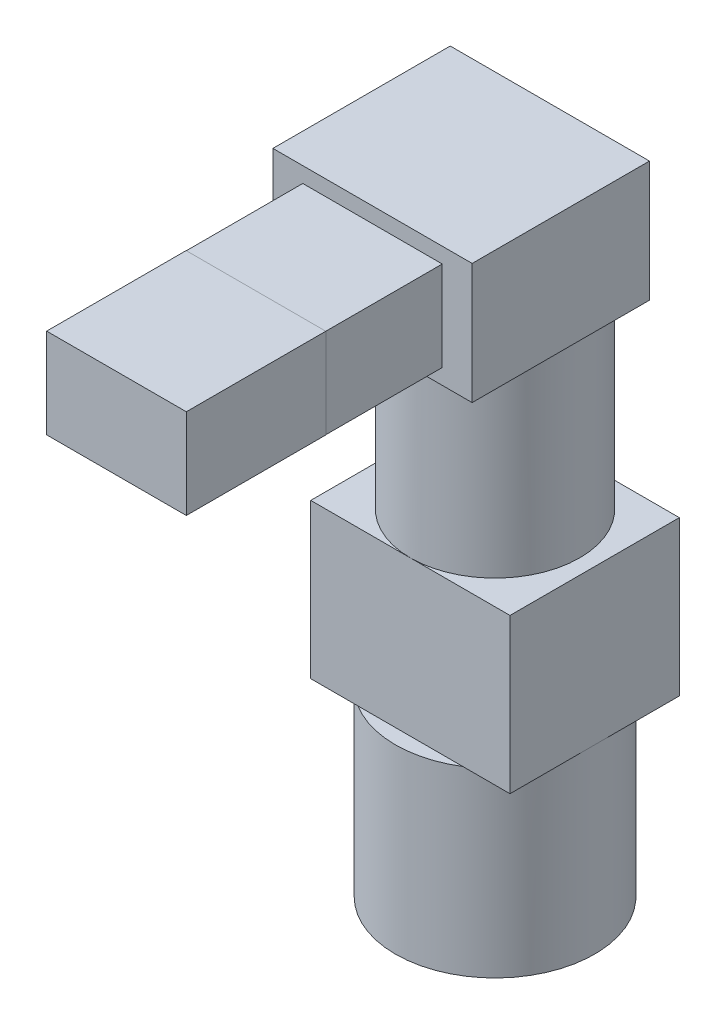
SolidWorks part; units mm, degrees
ref_plane "Front Plane" through (0, 0, 0) normal (0, 0, 1) x (1, 0, 0)
ref_plane "Top Plane" through (0, 0, 0) normal (0, 1, 0) x (1, 0, 0)
ref_plane "Right Plane" through (0, 0, 0) normal (1, 0, 0) x (0, 0, -1)
sketch "Sketch1" plane through (0, 0, 0) normal (0, 1, 0) x (1, 0, 0)
  circle A0 centre (0, 0) radius 50
extrude "Boss-Extrude1" add sketch "Sketch1" along normal blind 91
sketch "Sketch2" plane through (0, 0, 0) normal (1, 0, 0) x (0, 0, -1)
  line L0 (0, 47.4071) -> (0, 172.9241) construction
  line L1 (0, 50.05) -> (0, -50.05) construction
  line L2 (50, 91) -> (-50, 91) construction
  line L3 (42.5, 91) -> (-42.5, 91)
  line L4 (42.5, 91) -> (42.5, 168.5)
  line L5 (42.5, 168.5) -> (-42.5, 168.5)
  line L6 (-42.5, 91) -> (-42.5, 168.5)
  point P12 (0, 168.5)
  dimension "D1" = 77.5
  dimension "D2" = 85
extrude "Boss-Extrude2" add sketch "Sketch2" along normal blind 50 and the other way blind 50
ref_plane "Plane1" through (0, 135.5, 0) normal (0, 1, 0) x (1, 0, 0)
sketch "Sketch4" plane through (0, 135.5, 0) normal (0, 1, 0) x (1, 0, 0)
  circle A0 centre (0, 0) radius 42.5
extrude "Boss-Extrude3" add sketch "Sketch4" along normal blind 135
sketch "Sketch5" plane through (0, 0, 0) normal (1, 0, 0) x (0, 0, -1)
  line L0 (0, 248.4844) -> (0, 367.9713) construction
  line L1 (0, 55) -> (0, -55) construction
  line L2 (42.5, 270.5) -> (-42.5, 270.5) construction
  line L7 (-61.5, 331) -> (27.5, 331)
  line L8 (-61.5, 331) -> (-61.5, 270.5)
  line L9 (-61.5, 270.5) -> (27.5, 270.5)
  line L10 (27.5, 331) -> (27.5, 270.5)
  dimension "D1" = 61.5
  dimension "D2" = 89
  dimension "D3" = 60.5
extrude "Boss-Extrude4" add sketch "Sketch5" along normal blind 50 and the other way blind 50
ref_plane "Plane2" through (0, 300.75, 0) normal (0, 1, 0) x (1, 0, 0)
sketch "Sketch6" plane through (0, 0, 61.5) normal (0, 0, 1) x (1, 0, 0)
  line L0 (48.95, 300.75) -> (-48.95, 300.75) construction
  line L1 (-35, 323.25) -> (35, 323.25)
  line L2 (-35, 323.25) -> (-35, 278.25)
  line L3 (-35, 278.25) -> (35, 278.25)
  line L4 (35, 323.25) -> (35, 278.25)
  line L5 (-35, 323.25) -> (35, 278.25) construction
  line L6 (-35, 278.25) -> (35, 323.25) construction
  line L7 (0, -61.325) -> (0, 61.325) construction
  point P0 (0, 300.75)
  dimension "D1" = 45
  dimension "D2" = 70
extrude "Boss-Extrude5" add sketch "Sketch6" along normal blind 58.5
sketch "Sketch7" plane through (0, 0, 120) normal (0, 0, 1) x (1, 0, 0)
  line L0 (48.95, 300.75) -> (-48.95, 300.75) construction
  line L1 (-35.05, 323.3) -> (35.05, 323.3)
  line L2 (-35.05, 323.3) -> (-35.05, 278.2)
  line L3 (-35.05, 278.2) -> (35.05, 278.2)
  line L4 (35.05, 323.3) -> (35.05, 278.2)
  line L5 (-35.05, 323.3) -> (35.05, 278.2) construction
  line L6 (-35.05, 278.2) -> (35.05, 323.3) construction
  line L7 (0, -93.5) -> (0, 93.5) construction
  point P0 (0, 300.75)
  dimension "D1" = 70.1
  dimension "D2" = 45.1
extrude "Boss-Extrude6" add sketch "Sketch7" along normal blind 70
ref_plane "Plane3" through (0, 0, 17) normal (0, 0, -1) x (-1, 0, 0)
sketch "Sketch9" plane through (0, 0, 0) normal (1, 0, 0) x (0, 0, -1)
  line L0 (-47.3398, 135.5) -> (79.4066, 135.5) construction
  line L1 (0, 370.0672) -> (0, 135.5) construction
  line L2 (0, 55) -> (0, -55) construction
  line L3 (-120.4224, 91) -> (120.4224, 91) construction
  line L4 (-42.5, 91) -> (0, 91) construction
  line L5 (4.125, 135.5) -> (-4.125, 135.5) construction
  line L6 (0, 91) -> (0, -53.4945) construction
  line L7 (-120, 300.75) -> (-169.4975, 251.2525)
  line L8 (-120, 278.2) -> (-120, 323.3) construction
  line L9 (-190, 323.3) -> (-120, 323.3) construction
  line L10 (0, 135.5) -> (-116.8494, 252.3494)
  line L11 (-116.8494, 252.3494) -> (-251.1997, 117.9991)
  line L12 (-201.7022, 167.4966) -> (-201.7022, 97.4966)
  point P14 (0, 135.5)
  point P24 (-201.7022, 167.4966)
  dimension "D1" = 165.25
  dimension "D2" = 190
  dimension "D3" = 45
  dimension "D4" = 45
  dimension "D5" = 70
  dimension "D6" = 70
  dimension "D7" = 45
  dimension "D8" = 70
